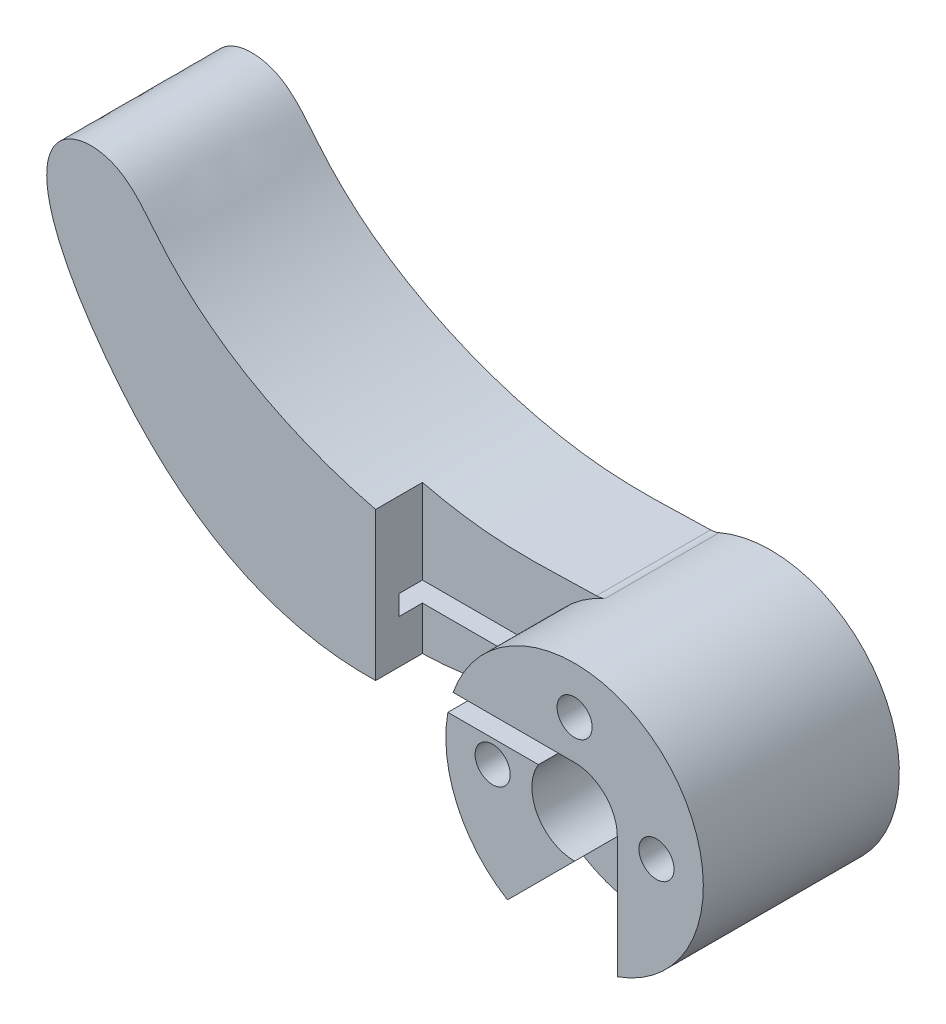
SolidWorks part; units mm, degrees
ref_plane "前视基准面" through (0, 0, 0) normal (0, 0, 1) x (1, 0, 0)
ref_plane "上视基准面" through (0, 0, 0) normal (0, 1, 0) x (1, 0, 0)
ref_plane "右视基准面" through (0, 0, 0) normal (1, 0, 0) x (0, 0, -1)
other "Configuration Table"
sketch "草图3" plane through (0, 0, 0) normal (0, 0, 1) x (1, 0, 0)
  arc A0 (-10, -25) -> (10, -25) centre (0, -25) ccw
  arc A1 (10, -25) -> (0, -15) centre (0, -25) ccw
  spline S0 degree 3 poles (0, -15) (-7.0325, -15) (-16.8635, -16.2801) (-34.3402, -9.8842) (-43.3409, 3.4479) (-53.0006, -1.1359) (-43, -14.4817) knots 0 0 0 0 0.248294 0.674131 0.760286 1 1 1 1
  spline S1 degree 3 poles (-10, -25) (-23.4998, -29.3314) (-34.4998, -25.8253) (-43, -14.4817) knots 0 0 0 0 1 1 1 1
  point P0 (0, 0)
  dimension "D3" = 43
  dimension "D1" = 10
  dimension "D2" = 25
extrude "凸台-拉伸2" add sketch "草图3" along normal blind 54.5
sketch "草图4" plane through (0, 0, 0) normal (0, 1, 0) x (1, 0, 0)
  line L0 (-48.1003, -54.5) -> (0, -54.5) construction
  line L1 (-20, -44.75) -> (10, -44.75)
  line L2 (-20, -44.75) -> (-20, -9.75)
  line L3 (-20, -9.75) -> (10, -9.75)
  line L4 (10, -44.75) -> (10, -9.75)
  line L6 (-48.1003, -27.25) -> (10, -27.25) construction
  line L8 (0, 0) -> (0, -54.5) construction
  line L10 (-48.1003, 0) -> (-48.1003, -54.5) construction
  dimension "D1" = 35
  dimension "D2" = 10
  dimension "D3" = 30
extrude "切除-拉伸2" cut sketch "草图4" against normal through all and the other way blind 5
sketch "草图6" plane through (0, 0, 44.75) normal (0, 0, -1) x (-1, 0, 0)
  circle A0 centre (0, -25) radius 10
  arc A1 (0, -15) -> (10, -25) centre (0, -25) ccw construction
extrude "凸台-拉伸3" add sketch "草图6" along normal blind 4
ref_plane "基准面1" through (0, 0, 27.25) normal (0, 0, -1) x (-1, 0, 0)
sketch "草图8" plane through (0, 0, 54.5) normal (0, 0, 1) x (1, 0, 0)
  line L0 (-10, -25) -> (10, -25) construction
  line L1 (0, -25) -> (0, 0) construction
  circle A1 centre (-7, -25) radius 2.7
  circle A2 centre (0, -18) radius 2.7
  circle A3 centre (7, -25) radius 2.7
  arc A4 (-10, -25) -> (0, -15) centre (0, -25) ccw construction
  point P19 (0, -25)
extrude "切除-拉伸4" cut sketch "草图8" against normal blind 13.25
mirror "镜向2" about plane through (0, 0, 27.25) normal (0, 0, -1) of "切除-拉伸4", "凸台-拉伸3"
sketch "草图5" plane through (0, 0, 54.5) normal (0, 0, 1) x (1, 0, 0)
  line L0 (-10, -25) -> (10, -25) construction
  line L1 (0, -18) -> (0, -25) construction
  circle A0 centre (0, -18) radius 1.5
  circle A1 centre (7, -25) radius 1.5
  circle A3 centre (-7, -25) radius 1.5
  arc A4 (-10, -25) -> (0, -15) centre (0, -25) ccw construction
  circle A5 centre (0, -32) radius 1.5 [skipped]
  point P16 (0, -25)
  dimension "D1" = 3
  dimension "D2" = 7
  dimension "D3" = 4
extrude "切除-拉伸5" cut sketch "草图5" against normal through all
sketch "草图9" plane through (0, 0, 54.5) normal (0, 0, 1) x (1, 0, 0)
  line L1 (17.5577, 3.2876) -> (-58.9198, 3.2876)
  line L2 (17.5577, 3.2876) -> (17.5577, -41.3354)
  line L3 (17.5577, -41.3354) -> (-58.9198, -41.3354)
  line L4 (-58.9198, 3.2876) -> (-58.9198, -41.3354)
extrude "切除-拉伸6" cut sketch "草图9" against normal up to surface (40.75 mm away) up to face at (1.5, -18, 13.75)
sketch "草图14" plane through (0, 0, 0) normal (0, 0, -1) x (-1, 0, 0)
  circle A0 centre (0, -25) radius 10
  circle A1 centre (0, -25) radius 11
extrude "凸台-拉伸5" add sketch "草图14" against normal up to surface (13.75 mm away) up to face at (1.5, -18, 13.75)
sketch "草图10" plane through (0, 0, 13.75) normal (0, 0, 1) x (1, 0, 0)
  line L2 (0, -21.35) -> (-30, -21.35)
  line L4 (-3.0854, -23.05) -> (-30, -23.05)
  line L5 (-30, -21.35) -> (-30, -23.05)
  arc A0 (-3.0854, -23.05) -> (0, -21.35) centre (0, -25) ccw
  point P5 (0, 0)
  dimension "D1" = 7.3
  dimension "D2" = 1.7
  dimension "D3" = 30
extrude "切除-拉伸7" cut sketch "草图10" against normal blind 7.5
sketch "草图12" plane through (0, 0, 13.75) normal (0, 0, 1) x (1, 0, 0)
  line L0 (-20, -23.05) -> (-20, -26.7886) construction
  line L1 (-20, -23.05) -> (-30, -23.05)
  line L2 (-20, -23.05) -> (-20, -21.35)
  line L3 (-20, -21.35) -> (-30, -21.35)
  line L4 (-30, -23.05) -> (-30, -21.35)
  line L5 (-30, -23.05) -> (-20, -23.05) construction
extrude "凸台-拉伸4" add sketch "草图12" against normal blind 2
sketch "草图15" plane through (0, 0, 13.75) normal (0, 0, 1) x (1, 0, 0)
  line L0 (3.65, -25) -> (3.65, -41.0299)
  line L1 (3.65, -25) -> (-9.5651, -38.2151)
  line L2 (-9.5651, -38.2151) -> (3.65, -41.0299)
  arc A0 (-3.0854, -23.05) -> (0, -21.35) centre (0, -25) ccw construction
  dimension "D1" = 45
extrude "切除-拉伸8" cut sketch "草图15" against normal blind 3.5
fillet "圆角1" radius 2 2 edges at (-10.9957, -25.3066, 4.875) (-4.726, -15.067, 4.875)
sketch "草图18" plane through (0, 0, 13.75) normal (0, 0, 1) x (1, 0, 0)
  line L2 (3.65, -25) -> (3.65, -35.3768)
  line L3 (-10.3768, -21.35) -> (0, -21.35)
  line L4 (3.65, -25) -> (3.65, -35.3768)
  line L5 (-10.3768, -21.35) -> (0, -21.35)
  line L6 (-5.736, -34.386) -> (0, -28.65)
  line L7 (-3.0854, -23.05) -> (-10.8258, -23.05)
  line L8 (-5.736, -34.386) -> (0, -28.65)
  line L9 (-3.0854, -23.05) -> (-10.8258, -23.05)
  circle A0 centre (-7, -25) radius 1.5 construction
  circle A1 centre (7, -25) radius 1.5 construction
  arc A2 (3.65, -35.3768) -> (-10.3768, -21.35) centre (0, -25) ccw
  arc A3 (3.65, -25) -> (0, -21.35) centre (0, -25) ccw
  arc A4 (3.65, -35.3768) -> (-10.3768, -21.35) centre (0, -25) ccw
  arc A5 (3.65, -25) -> (0, -21.35) centre (0, -25) ccw
  arc A6 (-3.0854, -23.05) -> (0, -28.65) centre (0, -25) ccw
  arc A7 (-10.8258, -23.05) -> (-5.736, -34.386) centre (0, -25) ccw
  arc A8 (-3.0854, -23.05) -> (0, -28.65) centre (0, -25) ccw
  arc A9 (-10.8258, -23.05) -> (-5.736, -34.386) centre (0, -25) ccw
  circle A10 centre (0, -18) radius 1.5 construction
  circle A11 centre (-7, -25) radius 1.5
  circle A12 centre (7, -25) radius 1.5
  circle A13 centre (0, -18) radius 1.5
  dimension "D1" = 0
  dimension "D2" = 0
extrude "凸台-拉伸7" add sketch "草图18" along normal blind 3
